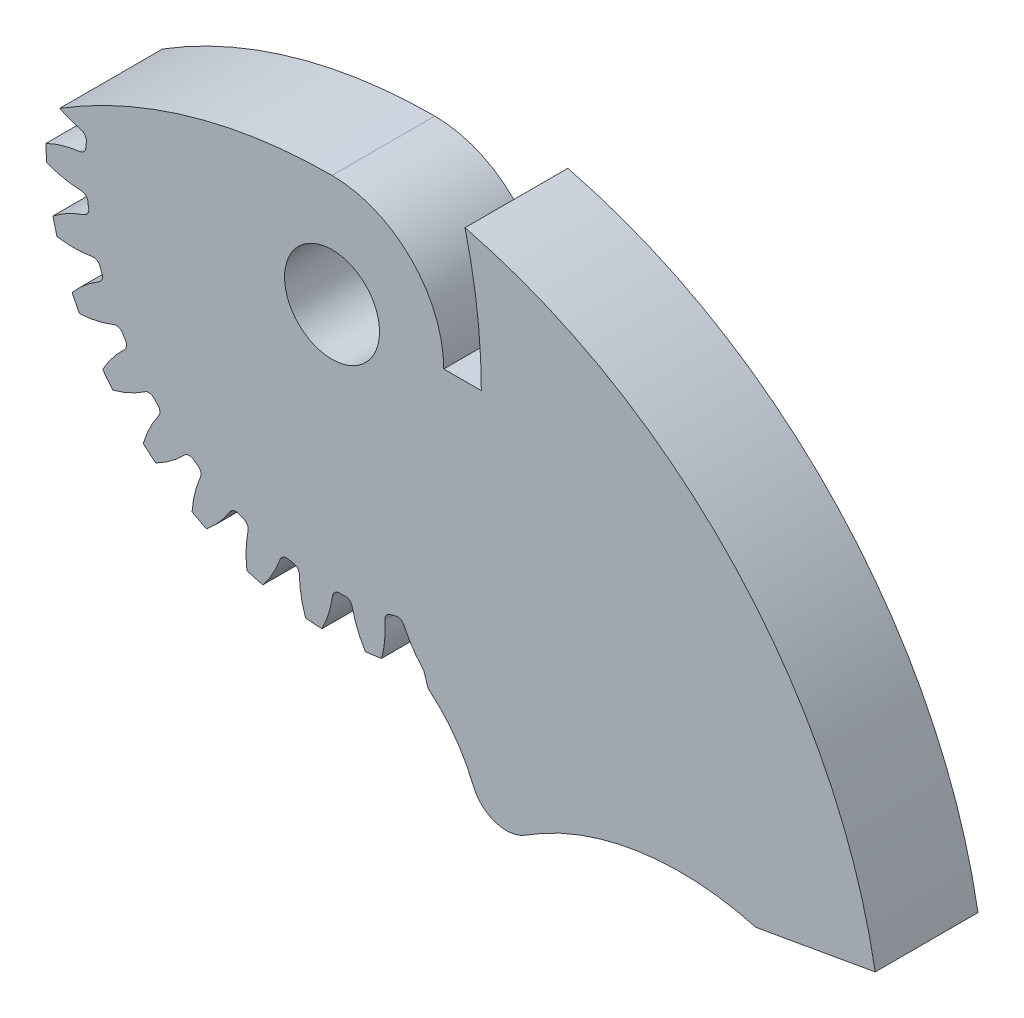
SolidWorks part; units mm, degrees
material "ABS"
ref_plane "Front" through (0, 0, 0) normal (0, 0, 1) x (1, 0, 0)
ref_plane "Top" through (0, 0, 0) normal (0, 1, 0) x (1, 0, 0)
ref_plane "Right" through (0, 0, 0) normal (1, 0, 0) x (0, 0, -1)
sketch "Sketch3" plane through (0, 0, 0) normal (0, 0, 1) x (1, 0, 0)
  circle A0 centre (0, 0) radius 40.64
  dimension "od" = 81.28
extrude "gearBody" add sketch "Sketch3" along normal blind 14.605
sketch "Sketch2" plane through (0, 0, 0) normal (0, 0, 1) x (1, 0, 0)
  line L0 (0, 0) -> (34.0786, 14.1158) construction
  line L1 (45.4751, -11.4855) -> (0, 0) construction
  line L2 (0, 0) -> (36.3143, 0) construction
  line L3 (38.0972, -0.458) -> (37.8451, -4.4001) construction
  line L5 (37.9712, -2.4291) -> (0, 0) construction
  line L7 (0, 0) -> (36.8864, 0) construction
  arc A0 (36.879, -0.7403) -> (36.6727, -3.9649) centre (0, 0) ccw construction
  arc A1 (40.637, 0.4947) -> (40.2427, -5.6687) centre (0, 0) ccw construction
  arc A2 (38.0972, -0.458) -> (37.8451, -4.4001) centre (0, 0) ccw construction
  arc A3 (34.9015, -2.6404) -> (34.9534, -1.8283) centre (0, 0) ccw
  arc A4 (45.4751, -11.4855) -> (35.6466, -3.6712) centre (32.0022, -18.3431) ccw
  arc A5 (45.4751, -11.4855) -> (46.5679, 5.5974) centre (0, 0) ccw
  arc A6 (46.5679, 5.5974) -> (35.8238, -0.9008) centre (34.0786, 14.1158) cw
  arc A7 (34.9534, -1.8283) -> (35.8238, -0.9008) centre (35.9376, -1.8798) cw
  arc A8 (35.6466, -3.6712) -> (34.9015, -2.6404) centre (35.8842, -2.7147) cw
  point P6 (46.5679, 5.5974)
  point P22 (45.4751, -11.4855)
  dimension "baseDia" = 73.7729
  dimension "od" = 81.28
  dimension "pd" = 76.2
  dimension "rd" = 70.0024
  dimension "rFillet" = 0.9855
  dimension "pointX" = 46.5679
  dimension "pointY" = 5.5974
  dimension "CTT" = 3.9421
  dimension "flankCenterAngle" = 22.5
extrude "toothCut" cut sketch "Sketch2" along normal through all
pattern_circular "CirPattern1" count 30 over 360 about axis through (0, 0, 14.605) along (0, 0, -1) of "toothCut"
sketch "hub1Dia" plane through (0, 0, 0) normal (0, 0, -1) x (-1, 0, 0)
  circle A0 centre (0, 0) radius 12.7
  dimension "hub1Dia" = 25.4
sketch "hub2Dia" plane through (0, 0, 14.605) normal (0, 0, 1) x (1, 0, 0)
  circle A0 centre (0, 0) radius 12.7
  dimension "hub2dia" = 25.4
sketch "boreDia" plane through (0, 0, 0) normal (0, 0, 1) x (1, 0, 0)
  circle A0 centre (0, 0) radius 6.7469
  dimension "boreDia" = 13.4937
extrude "bore" cut sketch "boreDia" against normal mid plane 25400
sketch "Sketch4" plane through (0, 0, 14.605) normal (0, 0, 1) x (1, 0, 0)
  circle A0 centre (0, -57.15) radius 78.359
  arc A2 (-42.9159, 8.4119) -> (42.9159, 8.4119) centre (0, 0) cw
  dimension "D1" = 156.718
  dimension "D2" = 57.15
extrude "Cut-Extrude1" cut sketch "Sketch4" against normal through all contours A0 region at (0, 27.8712, 14.605)
sketch "Sketch5" plane through (0, 0, 14.605) normal (0, 0, 1) x (1, 0, 0)
  line L0 (0, 21.209) -> (21.5163, 7.6712)
  line L1 (21.5163, 7.6712) -> (8.9608, -26.928)
  line L2 (8.9608, -26.928) -> (13.028, -38.4952)
  line L3 (0, 0) -> (0, -57.15) construction
  line L4 (0, -57.15) -> (-49.4328, 3.6491) construction
  line L5 (0, -57.15) -> (67.8609, -96.3295) construction
  line L6 (13.6543, -40.4261) -> (13.028, -38.4952)
  line L9 (0, -57.15) -> (77.1686, -43.5431) construction
  line L12 (60.232, -46.5295) -> (77.1686, -43.5431)
  circle A1 centre (0, -57.15) radius 78.359 construction
  arc A5 (0, 21.209) -> (77.1686, -43.5431) centre (0, -57.15) cw
  circle A6 centre (0, -57.15) radius 21.59 construction
  arc A10 (20.0525, -49.1485) -> (13.6543, -40.4261) centre (0, -57.15) ccw
  circle A12 centre (49.4934, -85.725) radius 40.64 construction
  arc A13 (27.5177, -51.539) -> (60.232, -46.5295) centre (49.4934, -85.725) cw
  arc A14 (27.5177, -51.539) -> (20.0525, -49.1485) centre (24.7708, -47.2658) cw
  point P28 (21.569, -56.1981)
  dimension "D1" = 43.18
  dimension "D3" = 81.28
  dimension "D7" = 5.08
  dimension "D6" = 156.718
  dimension "D2" = 120
  dimension "D4" = 57.15
  dimension "D5" = 80
extrude "Boss-Extrude1" add sketch "Sketch5" against normal up to surface (14.605 mm away) up to face at (6.7469, 0, 0)
sketch "Sketch6" plane through (0, 0, 14.605) normal (0, 0, 1) x (1, 0, 0)
  line L1 (-41.2829, 3.086) -> (-43.5386, 8)
  line L2 (15.875, 0) -> (21.209, 0)
  circle A0 centre (0, -57.15) radius 78.359 construction
  arc A1 (77.1686, -43.5431) -> (-36.286, 12.3011) centre (0, -57.15) ccw construction
  circle A2 centre (0, 0) radius 15.875 construction
  arc A3 (0, 15.875) -> (15.875, 0) centre (0, 0) cw
  arc A4 (18.8964, 18.8964) -> (-43.5386, 8) centre (0, -57.15) ccw
  arc A5 (0, 15.875) -> (-41.2829, 3.086) centre (0, -57.15) ccw
  circle A6 centre (0, 0) radius 21.209 construction
  circle A8 centre (-57.15, 0) radius 78.359 construction
  arc A9 (21.209, 0) -> (18.8964, 18.8964) centre (-57.15, 0) ccw
  dimension "D4" = 57.15
  dimension "D1" = 31.75
  dimension "D2" = 42.418
  dimension "D3" = 156.718
extrude "Cut-Extrude2" cut sketch "Sketch6" against normal through all
equation "\"Bodytube_OD\" = 6.17in"
equation "\"Bodytube_ID\" = 5.998in"
equation "\"Fwd_Tube_Length\" = 40in"
equation "\"Mid_Tube_Length\" = 1in"
equation "\"Aft_Section_Length\"= 39in"
equation "\"Mid_Coupler_Length\"= 13in"
equation "\"Aft_Lower_Length\"= 22in"
equation "\"AB_Coupler_OD_Length\"= 1in"
equation "\"AB_Coupling_Section_Length\"= 0.375in"
equation "\"AB_Coupler_Length\"= \"AB_Coupler_OD_Length\" + \"AB_Coupling_Section_Length\" * 2"
equation "\"Cutout_Angle\" = 80"
equation "\"AB_Paddle_Height\" = 0.575in"
equation "\"AB_Coupler_Num_Screws\"= 6"
equation "\"Num_Cutouts\" = 3"
equation "\"AB_Coupler_OD\"= 6.17in"
equation "\"AB_Coupler_ID\"= 5.75in"
equation "\"AB_Coupler_Surface_Diameter\"= 5.998in"
equation "\"AB_Coupling_Screw_Diameter\"= 0.1065in"
equation "\"AB_Central_Bushing_Length\" = .75in"
equation "\"Lead_Screw_Dist\" = 2.25in"
equation "\"Lead_Screw_Diam\" = (27/64)*1in"
equation "\"Lead_Screw_Length\" = (\"Mid_Coupler_Length\" + 2*0.375in + 2*0.5in)"
equation "\"Paddle_Pin_Offset\" = .25in"
equation "\"Paddle_Pin_Radius\" = 2.25in"
equation "\"Fwd_BKHD_From_Top\" = 18in"
equation "\"D1@Sketch4\"=\"Bodytube_OD\""
equation "\"D2@Sketch4\"=\"Paddle_Pin_Radius\""
equation "\"D3@Sketch5\"=\"Paddle_Gear_OD\""
equation "\"D4@Sketch5\"=\"Paddle_Pin_Radius\""
equation "\"Motor_OD\" = 4in"
equation "\"Aft_Upper_Length\"= \"Aft_Section_Length\" - \"Aft_Lower_Length\" - \"AB_Coupler_OD_Length\""
equation "\"Paddle_Gear_OD\" = 3.2in"
equation "\"D5@Sketch5\"=\"Cutout_Angle\""
equation "\"D6@Sketch5\"=\"Bodytube_OD\""
equation "\"D1@Sketch6\"=\"AB_Coupler_ID\"-2*\"Paddle_Pin_Radius\""
equation "\"D2@Sketch6\"=\"Bodytube_OD\"-2*\"Paddle_Pin_Radius\""
equation "\"D3@Sketch6\"=\"Bodytube_OD\""
equation "\"D4@Sketch6\"=\"Paddle_Pin_Radius\""
